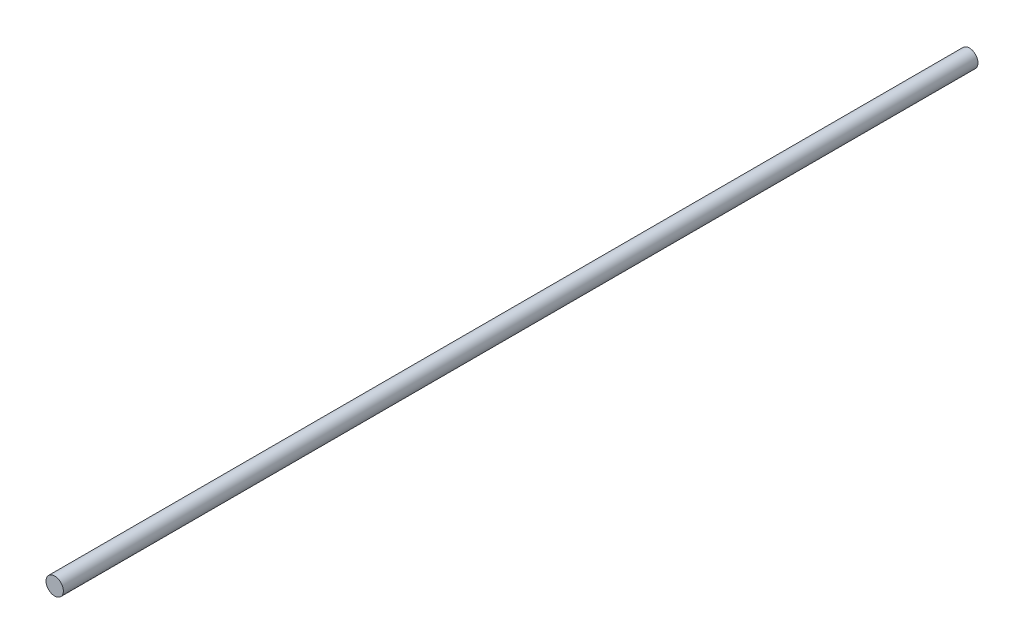
SolidWorks part; units mm, degrees
material "AISI 316 Stainless Steel Sheet (SS)"
ref_plane "Front (1)" through (0, 0, 0) normal (0, 0, 1) x (1, 0, 0)
ref_plane "Top (2)" through (0, 0, 0) normal (0, 1, 0) x (1, 0, 0)
ref_plane "Right (3)" through (0, 0, 0) normal (1, 0, 0) x (0, 0, -1)
ref_axis "X Axis" through (13.5064, 0, 0) along (-1, 0, 0)
ref_axis "Y Axis" through (0, 12.3593, 0) along (0, -1, 0)
ref_axis "Z Axis" through (0, 0, 14.1119) along (0, 0, -1)
sketch "Sketch2" plane through (0, 0, 0) normal (1, 0, 0) x (0, 0, -1)
  line L0 (-19.1, 0) -> (0, 0) construction
  line L1 (-19.1, 0) -> (402.3, 0)
  line L2 (-19.1, 0) -> (-19.1, 4)
  line L3 (-19.1, 4) -> (402.3, 4)
  line L4 (402.3, 0) -> (402.3, 4)
  line L5 (-16.1, 4) -> (-16.1, -4) construction
  line L6 (399.3, -4) -> (399.3, 4) construction
  dimension "D1" = 8
  dimension "D2" = 421.4
  dimension "D3" = 3
  dimension "D4" = 3
revolve "Revolve1" add sketch "Sketch2" angle 360 about L0
cosmetic thread "Cosmetic Thread2"
